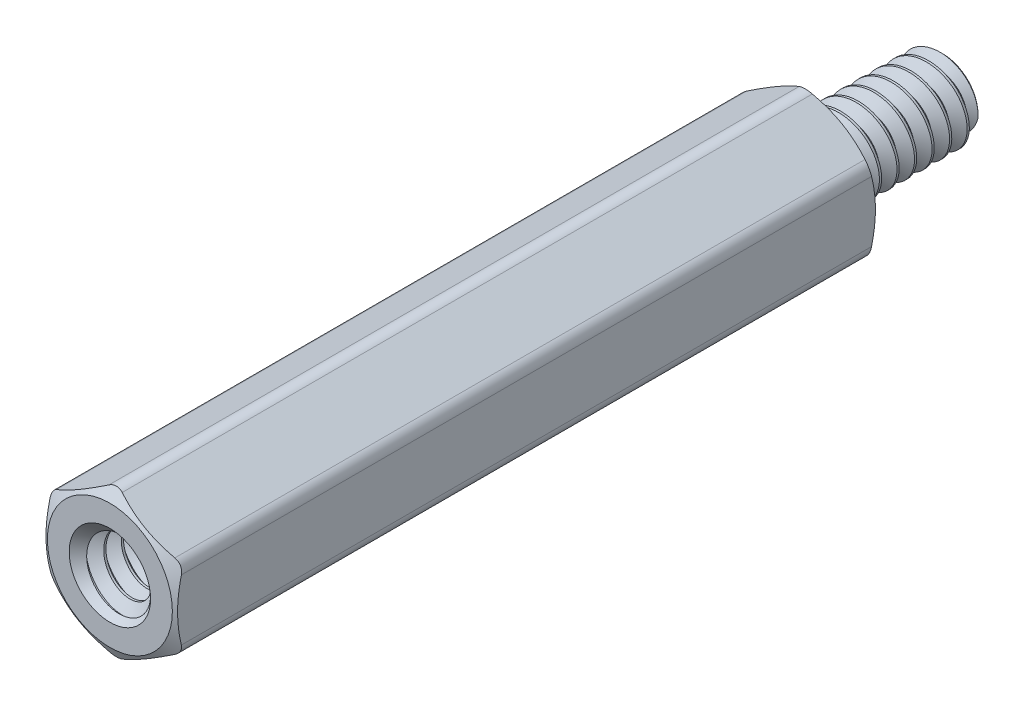
SolidWorks part; units mm, degrees
ref_plane "Front Plane" through (0, 0, 0) normal (0, 0, 1) x (1, 0, 0)
ref_plane "Top Plane" through (0, 0, 0) normal (0, 1, 0) x (1, 0, 0)
ref_plane "Right Plane" through (0, 0, 0) normal (1, 0, 0) x (0, 0, -1)
sketch "Sketch1" plane through (0, 0, 0) normal (0, 0, 1) x (1, 0, 0)
  line L1 (2.3813, 1.3748) -> (0, 2.7496)
  line L2 (0, 2.7496) -> (-2.3812, 1.3748)
  line L3 (-2.3812, 1.3748) -> (-2.3812, -1.3748)
  line L4 (-2.3812, -1.3748) -> (0, -2.7496)
  line L5 (0, -2.7496) -> (2.3813, -1.3748)
  line L6 (2.3813, -1.3748) -> (2.3813, 1.3748)
  circle A0 centre (0, 0) radius 2.3812 construction
  point P10 (0, -2.3812)
  dimension "Hex Size" = 4.7625
sketch "Sketch2" plane through (0, 0, 0) normal (1, 0, 0) x (0, 0, -1)
  line L0 (4.7625, 0) -> (-25.4, 0) construction
  line L2 (0, 1.4224) -> (0, -1.4224) construction
  line L3 (-19.05, 1.4224) -> (-19.05, -1.4224) construction
  line L4 (-25.9953, 1.4911) -> (-25.6778, 0.9412) construction
  line L5 (-25.6778, 0.9412) -> (-25.3603, 1.4911) construction
  line L6 (-25.3603, 1.4911) -> (-25.9953, 1.4911) construction
  line L7 (-25.9556, 1.4224) -> (-25.4, 1.4224) construction
  line L8 (-25.7175, 1.01) -> (-25.6381, 1.01) construction
  line L9 (-25.6778, 1.01) -> (-25.6778, 0.9412) construction
  line L10 (-25.6778, 1.4224) -> (-25.6778, 1.4911) construction
  line L11 (4.7228, 1.4911) -> (5.3578, 1.4911) construction
  line L12 (5.3578, 1.4911) -> (5.0403, 0.9412) construction
  line L13 (5.0403, 0.9412) -> (4.7228, 1.4911) construction
  line L14 (4.7625, 1.4224) -> (5.3181, 1.4224) construction
  line L15 (5.0006, 1.01) -> (5.08, 1.01) construction
  line L16 (5.0403, 1.01) -> (5.0403, 0.9412) construction
  line L17 (5.0403, 1.4224) -> (5.0403, 1.4911) construction
  line L18 (0, 2.7496) -> (-25.4, 2.7496) construction
  point P6 (0, 0)
  point P9 (-19.05, 0)
  dimension "Length" = 25.4
sketch "Sketch3" plane through (0, 0, 0) normal (1, 0, 0) x (0, 0, -1)
  line L0 (-19.05, 0) -> (4.7625, 0)
  line L1 (-19.05, 1.4224) -> (-19.05, -1.4224) construction
  line L2 (4.7625, 0) -> (4.7625, 1.2637)
  line L3 (4.7625, 1.2637) -> (4.6038, 1.4224)
  line L4 (4.6038, 1.4224) -> (0.8096, 1.4224)
  line L5 (0.8096, 1.4224) -> (0.5715, 1.01)
  line L6 (-19.05, 0) -> (-19.05, 1.2636)
  line L7 (-19.05, 1.2636) -> (-19.2087, 1.4224)
  line L8 (-19.2087, 1.4224) -> (-25.2413, 1.4224)
  line L9 (-25.2413, 1.4224) -> (-25.4, 1.5811)
  line L10 (4.6038, 0) -> (4.6038, -1.4224) construction
  line L11 (-25.4, 1.5811) -> (-25.4, 2.3812)
  line L12 (-25.4, 2.3812) -> (0, 2.3812)
  line L14 (0.5715, 1.01) -> (0.1587, 1.01)
  line L15 (0, 1.1687) -> (0, 2.3812)
  arc A0 (0, 1.1687) -> (0.1587, 1.01) centre (0.1587, 1.1687) ccw
  point P5 (-25.4, -2.3812)
  point P8 (-23.8125, -1.4224)
  point P9 (3.175, -1.4224)
  point P27 (0, 1.01)
  dimension "D4" = 0.1588
  dimension "D2" = 0.1588
  dimension "D1" = 45
  dimension "D6" = 1.5875
  dimension "D7" = 60
  dimension "D3" = 1.5875
  dimension "D5" = 0.5715
revolve "Revolve1" add sketch "Sketch3" angle 360 about L0 region at (0, 1.2091, 9.5169)
sketch "Sketch4" plane through (0, 0, 25.4) normal (0, 0, 1) x (1, 0, 0)
  line L0 (0, 2.3812) -> (0, 1.4224) construction
  line L1 (-2.3812, 1.3748) -> (-2.3812, -1.3748)
  line L2 (-2.3812, -1.3748) -> (0, -2.7496)
  line L3 (0, -2.7496) -> (2.3812, -1.3748)
  line L4 (2.3812, -1.3748) -> (2.3812, 1.3748)
  line L5 (2.3812, 1.3748) -> (0, 2.7496)
  line L6 (0, 2.7496) -> (-2.3812, 1.3748)
  circle A0 centre (0, 0) radius 2.3812 construction
  circle A1 centre (0, 0) radius 1.9018
  circle A2 centre (0, 0) radius 2.3812 construction
  point P16 (0, 1.9018)
extrude "Boss-Extrude1" add sketch "Sketch4" against normal up to surface (25.4 mm away) up to face at (0, 2.3812, 0)
sketch "Sketch5" plane through (0, 0, 25.4) normal (0, 0, 1) x (1, 0, 0)
  line L0 (-0.8159, 1.1652) -> (0.8159, -1.1652) construction
  line L1 (0, 1.4224) -> (0, -1.4224) construction
  line L3 (0, -2.9435) -> (0, 2.9435) construction
  circle A0 centre (0, 0) radius 2.2622
  point P11 (0.8159, -1.1652)
  dimension "D1" = 4.5244
  dimension "D2" = 35
extrude "Cut-Extrude1" cut sketch "Sketch5" against normal through all draft 60 flip side to cut
sketch "Sketch6" plane through (0, 0, 0) normal (0, 0, -1) x (-1, 0, 0)
  circle A0 centre (0, 0) radius 2.2622
  circle A1 centre (0, 0) radius 2.2622 construction
extrude "Cut-Extrude2" cut sketch "Sketch6" against normal through all draft 60 flip side to cut
fillet "Fillet1" radius 0.4763 6 edges at (0, 2.7496, 12.7) (-2.3812, -1.3748, 12.7) (0, -2.7496, 12.7) (2.3812, -1.3748, 12.7) (2.3812, 1.3748, 12.7) (-2.3812, 1.3748, 12.7)
sketch "Drawing1" plane through (0, 0, 0) normal (1, 0, 0) x (0, 0, -1)
  line L0 (-25.4, 1.4224) -> (-19.05, 1.4224) construction
  line L1 (-19.05, 1.4224) -> (-19.05, -1.4224) construction
  line L2 (-19.05, -1.4224) -> (-25.4, -1.4224) construction
sketch "Sketch7" plane through (0, 0, 0) normal (-1, 0, 0) x (0, 0, 1)
  line L0 (-5.0006, 1.01) -> (-5.08, 1.01)
  line L1 (-5.08, 1.01) -> (-5.338, 1.4568)
  line L2 (-5.3578, 1.4911) -> (-5.0403, 0.9412) construction
  line L3 (-5.338, 1.4568) -> (-4.7427, 1.4568)
  line L4 (-5.0403, 0.9412) -> (-4.7228, 1.4911) construction
  line L5 (-4.7427, 1.4568) -> (-5.0006, 1.01)
  line L6 (-5.0403, 1.4224) -> (-5.0403, 1.4911) construction
  point P12 (-5.0403, 1.4568)
sketch "Sketch8" plane through (0, 0, -4.7625) normal (0, 0, -1) x (-1, 0, 0)
  circle A0 centre (0, 0) radius 1.4224
curve "Helix/Spiral1" pitch 0.635 height 4.6196 radius 1.4224 centre (0, 0, -4.7625) axis (0, 0, 1) start towards (0, 1, 0)
sweep "Cut-Sweep1" cut profiles "Sketch7" path "Helix/Spiral1" align with end faces yes
sketch "Sketch9" plane through (0, 0, 19.05) normal (0, 0, 1) x (1, 0, 0)
  circle A0 centre (0, 0) radius 1.5811
extrude "Boss-Extrude2" add sketch "Sketch9" along normal up to surface (6.35 mm away) up to face at (0, 1.5811, 25.4)
sketch "Sketch10" plane through (0, 0, 0) normal (1, 0, 0) x (0, 0, -1)
  line L0 (4.7625, 0) -> (-25.4, 0) construction
  line L1 (-19.05, 1.4224) -> (-25.4, 1.4224)
  line L2 (-19.05, 1.4224) -> (-19.05, 0)
  line L3 (-19.05, 0) -> (-25.4, 0)
  line L4 (-25.4, 1.4224) -> (-25.4, 0)
revolve "Revolve2" add sketch "Sketch10" angle 360 about L0
sketch "Sketch11" plane through (0, 0, 25.4) normal (0, 0, 1) x (1, 0, 0)
  circle A0 centre (0, 0) radius 1.4224
  circle A1 centre (0, 0) radius 1.4224 construction
sketch "Sketch12" plane through (0, 0, 0) normal (1, 0, 0) x (0, 0, -1)
  line L0 (-25.7175, 1.01) -> (-25.6381, 1.01)
  line L1 (-25.6381, 1.01) -> (-25.3802, 1.4568)
  line L2 (-25.6778, 0.9412) -> (-25.3603, 1.4911) construction
  line L3 (-25.3802, 1.4568) -> (-25.9755, 1.4568)
  line L4 (-25.9953, 1.4911) -> (-25.6778, 0.9412) construction
  line L5 (-25.9755, 1.4568) -> (-25.7175, 1.01)
  line L6 (-25.6778, 1.4224) -> (-25.6778, 1.4911) construction
  point P12 (-25.6778, 1.4568)
curve "Helix/Spiral2" pitch 0.635 height 6.985 radius 1.4224 centre (0, 0, 25.4) axis (0, 0, -1) start towards (0, 1, 0)
sweep "Cut-Sweep2" cut profiles "Sketch12" path "Helix/Spiral2" align with end faces yes
combine bodies "Combine1" operation type subtract main body 113 bodies to subtract 114
sketch "Sketch13" plane through (0, 0, 25.4) normal (0, 0, 1) x (1, 0, 0)
  circle A0 centre (0, 0) radius 1.4732
  dimension "D1" = 0.0508
extrude "Cut-Extrude3" cut sketch "Sketch13" against normal through all draft 45
equation "\"Thread Pitch (B)/8@Sketch2\"=\"Thread Pitch (B)@Sketch2\"/8"
equation "\"Thread Pitch (A)/8@Sketch2\"=\"Thread Pitch (A)@Sketch2\"/8"
equation "\"D1@Sketch5\" = \"Hex Size@Sketch1\" * .95"
equation "\"D1@Fillet1\" = \"Hex Size@Sketch1\" * .1"
equation "\"D2@Sketch3\" = \"Thread Pitch (A)@Sketch2\" * .25"
equation "\"D4@Sketch3\" = \"D2@Sketch3\""
equation "\"D6@Sketch3\" = \"Thread Pitch (A)@Sketch2\" * 2.5"
equation "\"D3@Helix/Spiral1\" = \"Thread Length (A)@Sketch2\" - \"D5@Sketch3\" * .25"
equation "\"D4@Helix/Spiral1\" = \"Thread Pitch (A)@Sketch2\""
equation "\"D3@Sketch3\" = \"Thread Pitch (B)@Sketch2\" * 2.5"
equation "\"D5@Sketch3\" = \"Thread Length (A)@Sketch2\" * .12"
equation "\"D3@Helix/Spiral2\" = \"Minimum Thread Length (B)@Sketch2\" + \"Thread Pitch (B)@Sketch2\""
equation "\"D4@Helix/Spiral2\" = \"Thread Pitch (B)@Sketch2\""
